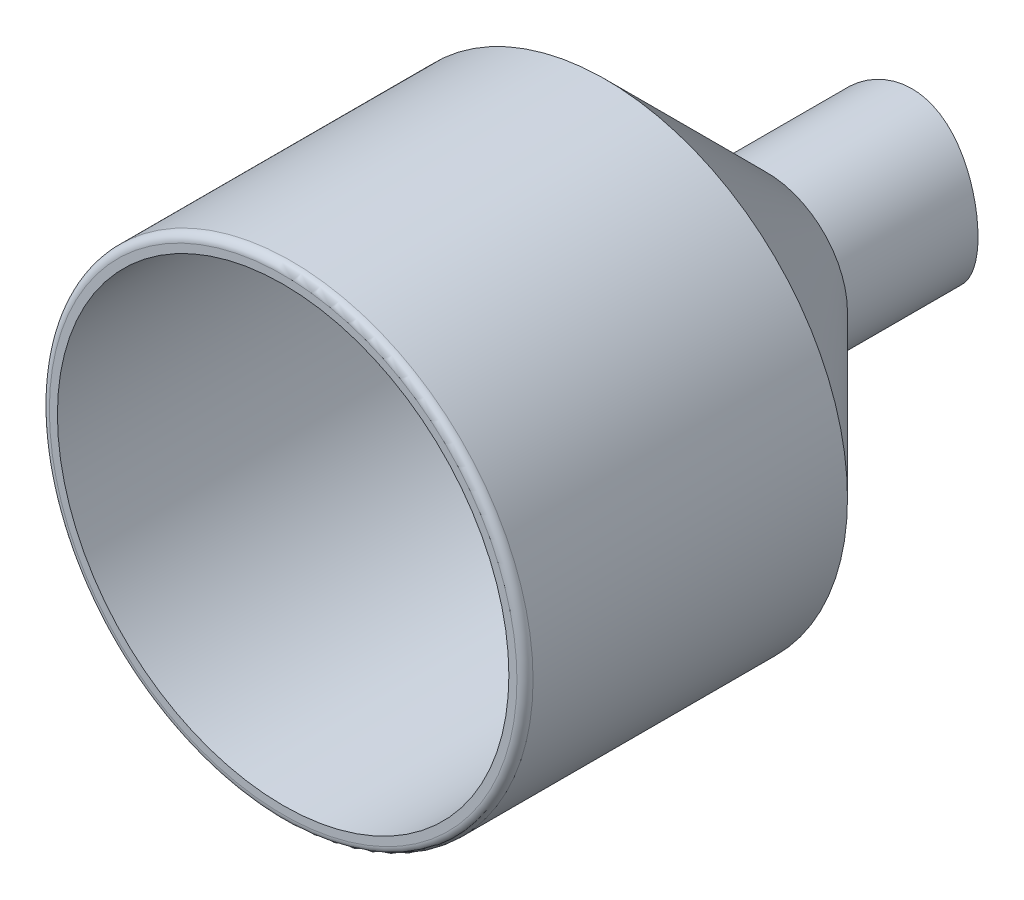
SolidWorks part; units mm, degrees
ref_plane "Front Plane" through (0, 0, 0) normal (0, 0, 1) x (1, 0, 0)
ref_plane "Top Plane" through (0, 0, 0) normal (0, 1, 0) x (1, 0, 0)
ref_plane "Right Plane" through (0, 0, 0) normal (1, 0, 0) x (0, 0, -1)
sketch "Sketch1" plane through (0, 0, 0) normal (0, 0, 1) x (1, 0, 0)
  circle A0 centre (0, 0) radius 15
  circle A1 centre (0, 0) radius 14
  dimension "D1" = 30
  dimension "D2" = 1
extrude "Boss-Extrude1" add sketch "Sketch1" along normal blind 20
sketch "Sketch2" plane through (0, 0, 0) normal (0, 0, -1) x (-1, 0, 0)
  circle A0 centre (0, 0) radius 15 construction
  point P0 (0, 0)
  point P1 (0, 15)
sketch "Sketch4" plane through (0, 0, 20) normal (0, 0, 1) x (1, 0, 0)
  point P0 (0, 15)
ref_plane "Plane1" through (0, 0, 0) normal (1, 0, 0) x (0, 0, -1)
sketch "Sketch5" plane through (0, 0, 0) normal (1, 0, 0) x (0, 0, -1)
  line L0 (0, 0) -> (30, 0) construction
  line L3 (10, 5) -> (0, 15)
  line L4 (0, -15) -> (0, 15) construction
  line L5 (0, 15) -> (0, 14)
  line L6 (0, 14) -> (10, 4)
  line L7 (10, 4) -> (10, 5)
  line L10 (10, 5) -> (19, 5)
  line L11 (10, 5) -> (10, 4)
  line L12 (10, 4) -> (19, 4)
  line L13 (19, 5) -> (19, 4)
  point P2 (0, 0)
  point P11 (0, 0)
  dimension "D1" = 10
  dimension "D2" = 9
  dimension "D3" = 4
fillet "Fillet1" radius 0.5 1 edges at (15, 0, 20)
revolve "Revolve1" add sketch "Sketch5" angle 360 about L0 region at (0, 9.5, -5) region at (0, 4.5, -14.5)
sketch "Sketch6" plane through (0, 0, 0) normal (1, 0, 0) x (0, 0, -1)
  line L2 (19, 5) -> (19, -5) construction
  circle A0 centre (32.344, 0) radius 14.25
  point P5 (19, 0)
  dimension "D1" = 28.5
extrude "Cut-Extrude1" cut sketch "Sketch6" against normal blind 10 and the other way blind 10
sketch "Sketch7" plane through (0, 0, 20) normal (0, 0, 1) x (1, 0, 0)
  line L1 (-3, -1) -> (-5, -1)
  line L2 (-3, -1) -> (-3, 1)
  line L3 (-3, 1) -> (-5, 1)
  line L4 (-5, -1) -> (-5, 1)
  line L5 (-3, -1) -> (-5, 1) construction
  line L6 (-3, 1) -> (-5, -1) construction
  line L7 (3, -1) -> (5, -1)
  line L8 (3, -1) -> (3, 1)
  line L9 (3, 1) -> (5, 1)
  line L10 (5, -1) -> (5, 1)
  line L11 (3, -1) -> (5, 1) construction
  line L12 (3, 1) -> (5, -1) construction
  circle A0 centre (0, 0) radius 5 construction
  circle A1 centre (0, 0) radius 5
  point P0 (-4, 0)
  point P5 (4, 0)
  dimension "D1" = 2
  dimension "D2" = 2
  dimension "D3" = 2
  dimension "D4" = 2
extrude "Boss-Extrude2" add sketch "Sketch7" against normal blind 7 from offset 30 contours L3 A1 L1 L2 | A1 L9 L8 L7 region at (-3.9835, 0, 20) region at (3.9835, 0, 20) offset against normal yes
chamfer "Chamfer1" distance 1 angle 45 2 edges at (-3, 0, -17) (3, 0, -17)
